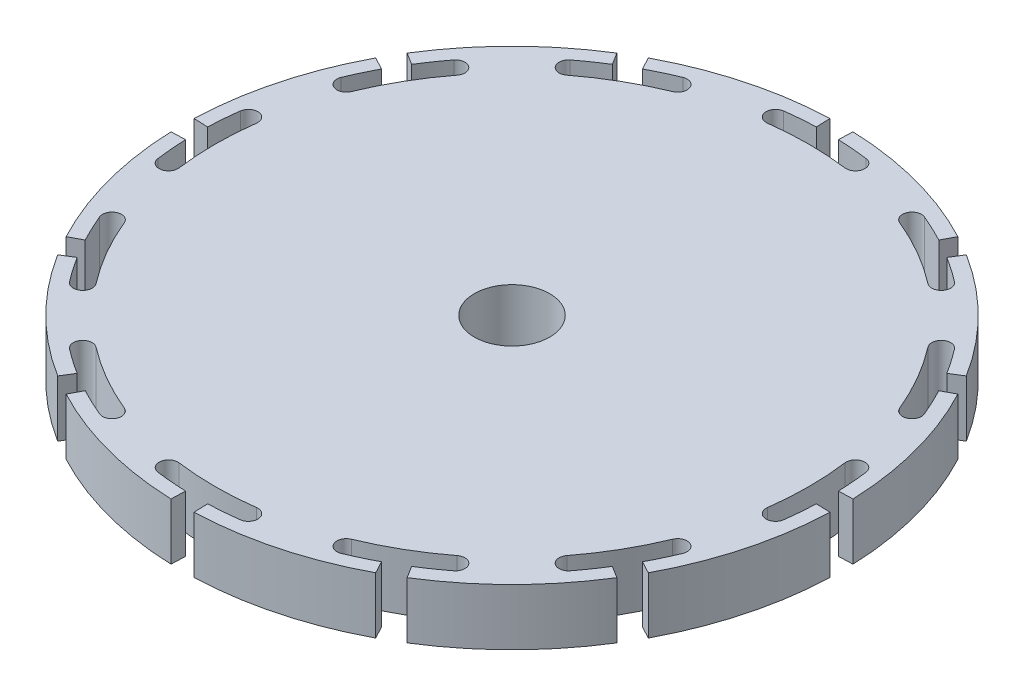
SolidWorks part; units mm, degrees
ref_plane "Front Plane" through (0, 0, 0) normal (0, 0, 1) x (1, 0, 0)
ref_plane "Top Plane" through (0, 0, 0) normal (0, 1, 0) x (1, 0, 0)
ref_plane "Right Plane" through (0, 0, 0) normal (1, 0, 0) x (0, 0, -1)
sketch "Sketch1" plane through (0, 0, 0) normal (0, 1, 0) x (1, 0, 0)
  circle A0 centre (0, 0) radius 35
  dimension "D1" = 70
sketch "Sketch2" plane through (0, 0, 0) normal (0, 1, 0) x (1, 0, 0)
  line L0 (0, 0) -> (0, 35) construction
  line L1 (-1.2215, 34.9787) -> (0, 0) construction
  line L2 (0, 0) -> (-4.5684, 34.7006) construction
  line L3 (-1.2215, 34.9787) -> (-1.1691, 33.4796)
  line L4 (0, 0) -> (4.5684, 34.7006) construction
  line L5 (1.2215, 34.9787) -> (0, 0) construction
  line L6 (1.2215, 34.9787) -> (1.1691, 33.4796)
  arc A0 (4.1116, 31.2305) -> (-4.1116, 31.2305) centre (0, 0) ccw
  circle A1 centre (0, 0) radius 35 construction
  arc A2 (-1.2215, 34.9787) -> (1.2215, 34.9787) centre (0, 0) cw
  arc A3 (-1.1691, 33.4796) -> (-4.3726, 33.2134) centre (0, 0) ccw
  arc A4 (-4.1116, 31.2305) -> (-4.3726, 33.2134) centre (-4.2421, 32.222) cw
  arc A5 (4.1116, 31.2305) -> (4.3726, 33.2134) centre (4.2421, 32.222) ccw
  arc A6 (1.1691, 33.4796) -> (4.3726, 33.2134) centre (0, 0) cw
  point P130 (0, 0)
  dimension "D1" = 15
  dimension "D2" = 2
  dimension "D4" = 1.5
  dimension "D3" = 4
sketch "Sketch3" plane through (0, 0, 0) normal (0, 1, 0) x (1, 0, 0)
  circle A0 centre (0, 0) radius 4
  dimension "D1" = 8
extrude "Wheel Blank" add sketch "Sketch1" along normal blind 6
extrude "T-Slot" cut sketch "Sketch2" along normal through all
pattern_circular "CirPattern1" count 12 over 360 about axis through (0, 6, 0) along (0, -1, 0) of "T-Slot"
extrude "Center Hole" cut sketch "Sketch3" along normal blind 6
